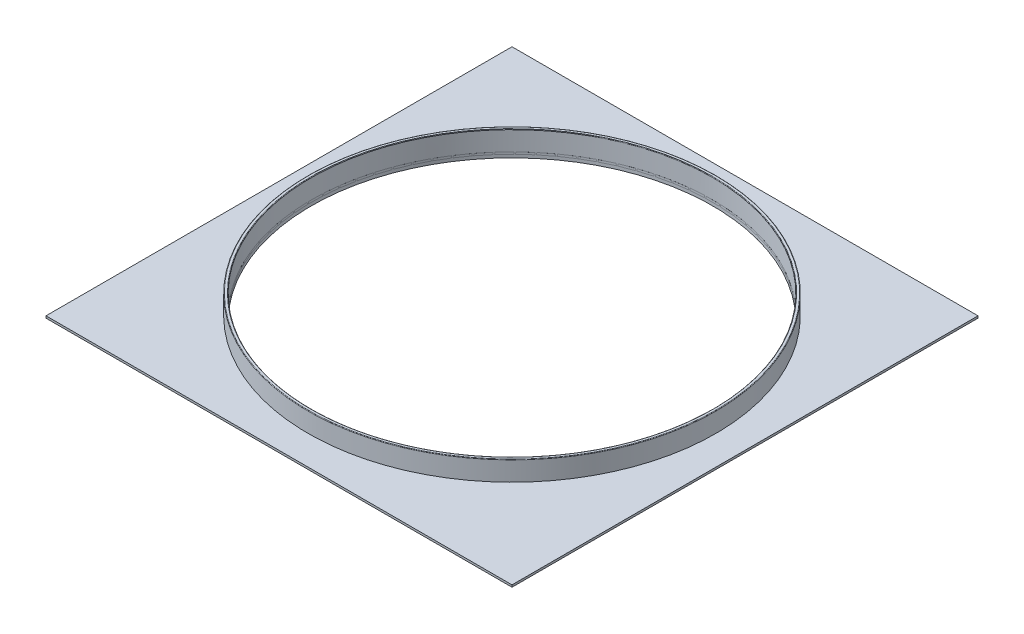
SolidWorks part; units mm, degrees
ref_plane "Front Plane" through (0, 0, 0) normal (0, 0, 1) x (1, 0, 0)
ref_plane "Top Plane" through (0, 0, 0) normal (0, 1, 0) x (1, 0, 0)
ref_plane "Right Plane" through (0, 0, 0) normal (1, 0, 0) x (0, 0, -1)
sketch "Sketch1" plane through (0, 0, 0) normal (1, 0, 0) x (0, 0, -1)
  line L0 (306.3875, 0) -> (349.25, 0)
  line L1 (349.25, 0) -> (349.25, 4.7625)
  line L2 (349.25, 4.7625) -> (311.15, 4.7625)
  line L3 (311.15, 4.7625) -> (311.15, 38.1)
  line L4 (311.15, 38.1) -> (306.3875, 38.1)
  line L5 (0, 38.1) -> (0, 0) construction
  line L6 (0, 50.5185) -> (0, -6.35) construction
  line L7 (306.3875, 38.1) -> (306.3875, 0)
  dimension "Flange Thk" = 4.7625
  dimension "Depth" = 38.1
  dimension "Flange Ht" = 38.1
  dimension "D1" = 4.7625
  dimension "D2" = 6.35
  dimension "ID" = 612.775
revolve "Revolve1" add sketch "Sketch1" angle 360 about L5
sketch "Sketch2" plane through (0, 38.1, 0) normal (0, 1, 0) x (1, 0, 0)
  line L0 (12.7, 0) -> (306.3875, 0) construction
  circle A0 centre (0, 0) radius 115.8875
  circle A1 centre (0, 0) radius 306.3875 construction
  circle A2 centre (0, 0) radius 349.25 construction
  dimension "D1" = 293.6875
  dimension "ID" = 231.775
fillet "Fillet3" radius 0.7938 2 edges at (0, 0, 349.25) (0, 4.7625, 349.25)
fillet "Fillet4" radius 0.7938 3 edges at (0, 38.1, 311.15) (0, 4.7625, 311.15) (0, 38.1, 306.3875)
sketch "Sketch3" plane through (0, 4.7625, 0) normal (0, 1, 0) x (-1, 0, 0)
  circle A0 centre (0, -328.6125) radius 5.5563
  circle A1 centre (0, 0) radius 328.6125 construction
  dimension "mounting hole size" = 11.1125
  dimension "BoltCircle" = 657.225
extrude "Cut-Extrude1" cut sketch "Sketch3" against normal through all
pattern_circular "CirPattern1" count 12 over 360 about axis through (0, 38.1, 0) along (0, 1, 0) of "Cut-Extrude1"
sketch "Sketch4" plane through (0, 4.7625, 0) normal (0, 1, 0) x (1, 0, 0)
  line L1 (-355.6, 355.6) -> (355.6, 355.6)
  line L2 (-355.6, 355.6) -> (-355.6, -355.6)
  line L3 (-355.6, -355.6) -> (355.6, -355.6)
  line L4 (355.6, 355.6) -> (355.6, -355.6)
  line L5 (-355.6, 355.6) -> (355.6, -355.6) construction
  line L6 (-355.6, -355.6) -> (355.6, 355.6) construction
  circle A0 centre (0, 0) radius 306.3875 construction
  circle A1 centre (0, 0) radius 306.3875
  point P0 (0, 0)
  dimension "D1" = 711.2
  dimension "D2" = 711.2
extrude "Boss-Extrude1" add sketch "Sketch4" along normal blind 3.175 separate body
equation "\"D1@Fillet3\" = \"Flange Thk@Sketch1\"/6"
equation "\"D1@Fillet4\" = \"Flange Thk@Sketch1\"/6"
equation "\"D1@Sketch1\" = \"Flange Thk@Sketch1\""
